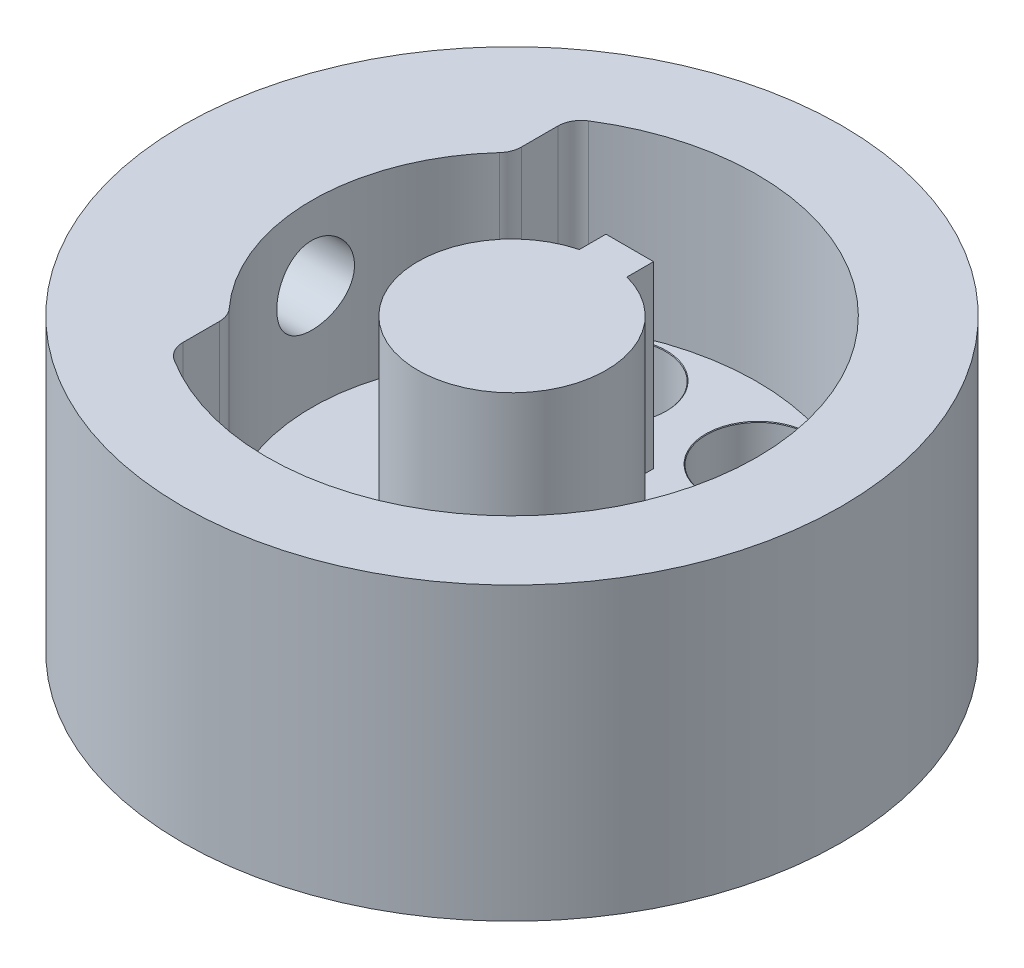
SolidWorks part; units mm, degrees
ref_plane "Front Plane" through (0, 0, 0) normal (0, 0, 1) x (1, 0, 0)
ref_plane "Top Plane" through (0, 0, 0) normal (0, 1, 0) x (1, 0, 0)
ref_plane "Right Plane" through (0, 0, 0) normal (1, 0, 0) x (0, 0, -1)
sketch "Sketch1" plane through (0, 0, 0) normal (0, 1, 0) x (1, 0, 0)
  line L0 (0, 8) -> (0, -8) construction
  line L1 (7.391, 3.0615) -> (-3.0615, 7.391) construction
  line L2 (7.391, 3.0615) -> (3.0615, -7.391) construction
  line L3 (3.0615, -7.391) -> (-7.391, -3.0615) construction
  line L4 (-3.0615, 7.391) -> (-7.391, -3.0615) construction
  line L5 (7.391, 3.0615) -> (-7.391, -3.0615) construction
  line L6 (3.0615, -7.391) -> (-3.0615, 7.391) construction
  line L7 (-8, 0) -> (8, 0) construction
  line L9 (3.0615, 7.391) -> (-7.391, 3.0615) construction
  line L10 (3.0615, 7.391) -> (7.391, -3.0615) construction
  line L11 (7.391, -3.0615) -> (-3.0615, -7.391) construction
  line L12 (-7.391, 3.0615) -> (-3.0615, -7.391) construction
  line L13 (3.0615, 7.391) -> (-3.0615, -7.391) construction
  line L14 (7.391, -3.0615) -> (-7.391, 3.0615) construction
  circle A0 centre (0, 0) radius 14
  circle A1 centre (0, 0) radius 8 construction
  dimension "D1" = 28
  dimension "D2" = 16
  dimension "D3" = 22.5
  dimension "D4" = 22.5
  dimension "D5" = 90
extrude "Boss-Extrude1" add sketch "Sketch1" against normal blind 4.75 contours A0
sketch "Sketch4" plane through (0, 0, 0) normal (0, 1, 0) x (1, 0, 0)
  line L1 (1.01, 5) -> (-1.01, 5)
  line L2 (1.01, 5) -> (1.01, 3.8704)
  line L3 (1.01, 3.8704) -> (-1.01, 3.8704)
  line L4 (-1.01, 5) -> (-1.01, 3.8704)
  line L5 (1.01, 5) -> (-1.01, 3.8704) construction
  line L6 (1.01, 3.8704) -> (-1.01, 5) construction
  circle A0 centre (0, 0) radius 4
  point P3 (0, 4.4352)
  dimension "D1" = 8
  dimension "D2" = 1.1296
  dimension "D3" = 2.02
extrude "Boss-Extrude4" add sketch "Sketch4" along normal blind 7.6142 contours L3 A0 | A0 L2 L1 L4 | L3 A0 region at (0, 0, -4.4778) region at (0, 0, 0.0137) region at (0, 0, -3.9223)
sketch "Sketch5" plane through (0, 0, 0) normal (0, 1, 0) x (1, 0, 0)
  line L0 (0, 0) -> (-9.8995, 9.8995)
  line L1 (0, 0) -> (-9.8995, -9.8995)
  line L2 (0, 0) -> (-14, 0) construction
  line L3 (-6.0104, 12.6442) -> (-6.0104, 6.0104)
  line L4 (-6.0104, -6.0104) -> (-6.0104, -12.6442)
  circle A0 centre (0, 0) radius 8.5
  circle A1 centre (0, 0) radius 14
  circle A2 centre (0, 0) radius 14 construction
  circle A3 centre (0, 0) radius 10.4
  circle M5 centre (0, 0) radius 14
  dimension "D1" = 17
  dimension "D2" = 20.8
  dimension "D3" = 45
  dimension "D4" = 45
extrude "Boss-Extrude5" add sketch "Sketch5" along normal blind 7.6142 contours L2 A0 L0 A1 | A0 L2 A1 L1 | L3 L0 M5 | L4 L1 M5 | L2 A3 L0 M5 | A3 L2 A1 L1 | L3 A3 L0 | L1 A3 L4 | A3 L4 L3 M5 region at (-8.5367, 0, -3.536) region at (-6.4642, 0, -7.3004) region at (-6.4642, 0, 7.3004) region at (-8.5367, 0, 3.536) region at (-11.0636, 0, -4.5827) region at (-7.4663, 0, -9.9374) region at (-5.6663, 0, -10.5658) region at (-7.4663, 0, 9.9374) region at (-11.0636, 0, 4.5827)
ref_plane "Plane1" through (-20, 0, 0) normal (1, 0, 0) x (0, 0, -1)
sketch "Sketch11" plane through (-20, 0, 0) normal (1, 0, 0) x (0, 0, -1)
  line L0 (0, 4.4892) -> (0, 7.6142) construction
  line L1 (14, 7.6142) -> (-14, 7.6142) construction
  circle A0 centre (0, 4.4892) radius 2 construction
  dimension "D2" = 4
  dimension "D1" = 3.125
hole_wizard "Tap Drill for M4x0.7 Tap2" positions "Sketch15" profile "Sketch17" hole size "M4x0.7" standard "ANSI Metric"
sketch "Sketch15" plane through (-20, 0, 0) normal (1, 0, 0) x (0, 0, -1)
  point P0 (0, 4.4892)
sketch "Sketch17" plane through (-20, 4.4892, 0) normal (0, 1, 0) x (0, 0, 1)
  line L0 (0, 0) -> (0, 14.7404)
  line L1 (0, 14.7404) -> (1.65, 13.749)
  line L2 (1.65, 13.749) -> (1.65, 0.025)
  line L3 (1.65, 0.025) -> (1.675, 0)
  line L5 (1.675, 0) -> (0, 0)
  line L6 (-1.65, 0.025) -> (-1.675, 0) construction
  line L10 (0, 14.7404) -> (-1.65, 13.749) construction
  line L11 (0, -6.35) -> (0, 107.95) construction
  dimension "Hole Dia." = 3.3
  dimension "Hole Depth" = 13.749
  dimension "Near C'Sink Dia." = 3.35
  dimension "Near C'Sink Angle" = 90
  dimension "Drill Angle" = 118
fillet "Fillet2" radius 1 4 edges at (-6.0104, 3.8071, 8.4873) (-6.0104, 3.8071, 6.0104) (-6.0104, 3.8071, -6.0104) (-6.0104, 3.8071, -8.4873)
hole_wizard "CBORE for M2 SHCS3" positions "Sketch18" profile "Sketch19" counterbore size "M2" standard "ANSI Metric"
sketch "Sketch18" plane through (0, 0, 0) normal (0, 1, 0) x (1, 0, 0)
  point P0 (-3.0615, 7.391)
  point P3 (3.0615, 7.391)
  point P6 (7.391, 3.0615)
  point P9 (7.391, -3.0615)
  point P12 (3.0615, -7.391)
  point P15 (-3.0615, -7.391)
sketch "Sketch19" plane through (-3.0615, 0, -7.391) normal (1, 0, 0) x (0, 0, 1)
  line L0 (0, 0) -> (0, 5.471)
  line L1 (0, 5.471) -> (1.2, 4.75)
  line L2 (1.2, 4.75) -> (1.2, 3.5)
  line L3 (1.2, 3.5) -> (2.2, 3.5)
  line L5 (2.2, 3.5) -> (2.2, 0.025)
  line L6 (2.2, 0.025) -> (2.225, 0)
  line L7 (2.225, 0) -> (0, 0)
  line L8 (-2.2, 0.025) -> (-2.225, 0) construction
  line L10 (0, 5.471) -> (-1.2, 4.75) construction
  line L11 (0, -6.35) -> (0, 107.95) construction
  dimension "Hole Dia." = 2.4
  dimension "Hole Depth" = 4.75
  dimension "C'Bore Dia." = 4.4
  dimension "C'Bore Depth" = 3.5
  dimension "Near C'Sink Dia." = 4.45
  dimension "Near C'Sink Angle" = 90
  dimension "Drill Angle" = 118
sketch "Sketch20" plane through (0, -4.75, 0) normal (0, -1, 0) x (1, 0, 0)
  circle A0 centre (0, 0) radius 4
  dimension "D1" = 8
extrude "Cut-Extrude2" cut sketch "Sketch20" against normal blind 2.75 contours A0
sketch "Sketch21" plane through (0, -2, 0) normal (0, -1, 0) x (-1, 0, 0)
  circle A0 centre (0, 0) radius 2
  dimension "D1" = 4
extrude "Cut-Extrude3" cut sketch "Sketch21" against normal blind 2.5
